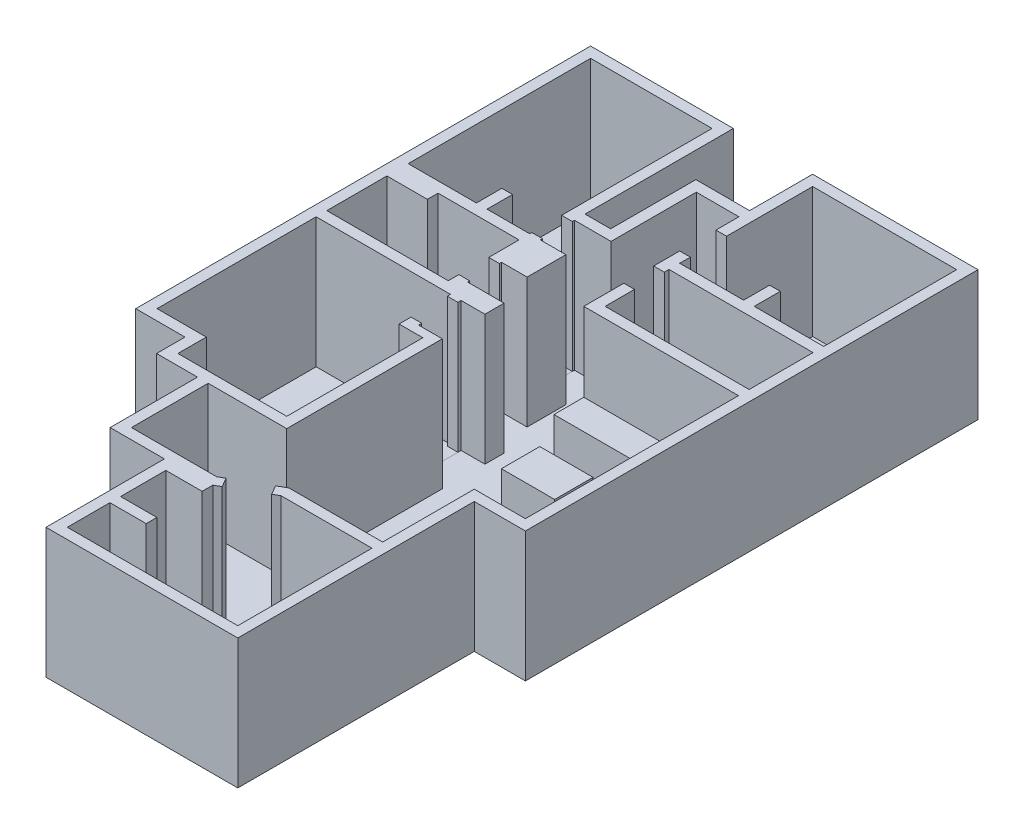
SolidWorks part; units mm, degrees
other "Long Room"
other "Corner Room"
other "Bathroom 1"
other "Big Room"
other "Window Room"
other "Walls"
other "Window Room Closet"
other "Long Room Closet"
other "Corner Room Closet"
other "Big Room Closet"
other "Bathroom 2"
ref_plane "Front Plane" through (0, 0, 0) normal (0, 0, 1) x (1, 0, 0)
ref_plane "Top Plane" through (0, 0, 0) normal (0, 1, 0) x (1, 0, 0)
ref_plane "Right Plane" through (0, 0, 0) normal (1, 0, 0) x (0, 0, -1)
sketch "Sketch1" plane through (0, 0, 0) normal (0, 1, 0) x (1, 0, 0)
  line L0 (0, 0) -> (0, -4280)
  line L1 (0, 0) -> (8590, 0) construction
  line L2 (0, 0) -> (0, -15669) construction
  line L3 (0, -15669) -> (8590, -15669) construction
  line L4 (8590, 0) -> (8590, -15669) construction
  line L5 (0, -4280) -> (1600, -4280)
  line L6 (1600, -4280) -> (1600, -3683)
  line L7 (1600, -3683) -> (1850, -3683)
  line L8 (2850, 0) -> (2850, -3530)
  line L9 (2850, -3530) -> (3100, -3530)
  line L11 (6710, -2510) -> (6710, -3120)
  line L12 (6710, -3120) -> (5210, -3120)
  line L13 (5210, -3480) -> (5210, -3370)
  line L14 (2850, 0) -> (0, 0)
  line L15 (5210, 0) -> (8590, 0)
  line L16 (8590, 0) -> (8590, -3120)
  line L17 (4241, -13106.5805) -> (4241, -13356.5805)
  line L18 (4116, -12890.0742) -> (4255.9329, -12809.2839)
  line L22 (8590, -3370) -> (8590, -4870)
  line L23 (5210, -4870) -> (8590, -4870)
  line L25 (0, -6190) -> (2850, -6190)
  line L26 (2850, -6190) -> (2850, -5940)
  line L27 (2850, -4530) -> (950, -4530)
  line L28 (0, -4780) -> (0, -6190)
  line L29 (950, -4530) -> (950, -4780)
  line L30 (1600, -3683) -> (0, -3683)
  line L31 (4255.9329, -12809.2839) -> (4380.9329, -13025.7903)
  line L32 (4241, -14419) -> (3390, -14419)
  line L33 (1850, -3683) -> (1850, -4280)
  line L34 (1850, -4280) -> (2850, -4280)
  line L35 (2850, -4280) -> (2850, -4230)
  line L36 (2850, -4230) -> (3100, -4230)
  line L37 (3100, -4230) -> (3100, -4280)
  line L38 (3100, -4280) -> (3700, -4280)
  line L39 (3100, -3530) -> (3100, -3480)
  line L40 (3100, -3480) -> (3960, -3480)
  line L41 (3960, -3480) -> (3960, -1480)
  line L42 (3960, -1480) -> (4960, -1480)
  line L43 (4960, -1480) -> (4960, -2020)
  line L45 (5210, -3120) -> (5210, -2870)
  line L46 (5210, -2870) -> (4960, -2870)
  line L47 (4960, -2870) -> (4960, -3480)
  line L48 (4960, -3480) -> (5210, -3480)
  line L49 (5210, -3480) -> (5210, -3370)
  line L50 (5210, -3370) -> (8590, -3370)
  line L51 (3700, -4280) -> (3700, -5190)
  line L52 (4960, -4180) -> (5210, -4180)
  line L53 (5210, -4180) -> (5210, -4870)
  line L54 (4960, -4180) -> (4960, -5120)
  line L55 (4960, -5120) -> (8590, -5120)
  line L56 (3700, -5190) -> (3100, -5190)
  line L57 (3100, -5190) -> (3100, -5240)
  line L58 (3100, -5240) -> (2850, -5240)
  line L59 (2850, -5240) -> (2850, -4530)
  line L60 (2850, -5940) -> (3100, -5940)
  line L61 (950, -4780) -> (0, -4780)
  line L62 (3100, -5940) -> (3100, -5990)
  line L63 (3100, -5990) -> (3960, -5990)
  line L64 (3960, -5990) -> (3960, -6440)
  line L65 (3960, -6440) -> (3401.2, -6440)
  line L66 (3401.2, -6440) -> (3401.2, -6515)
  line L67 (3401.2, -6515) -> (3151.2, -6515)
  line L68 (3151.2, -6515) -> (3151.2, -6440)
  line L69 (3151.2, -6440) -> (0, -6440)
  line L70 (1155.7, -10840.0742) -> (3710, -10840.0742)
  line L71 (3401.2, -7440) -> (3401.2, -7365)
  line L72 (3401.2, -7440) -> (3960, -7440)
  line L73 (3960, -7440) -> (3960, -11090.0742)
  line L74 (4380.9329, -13025.7903) -> (4241, -13106.5805)
  line L75 (3390, -14669) -> (4241, -14669)
  line L77 (4241, -14419) -> (4241, -14669)
  line L78 (3390, -14669) -> (3390, -15669)
  line L79 (3401.2, -7365) -> (3151.2, -7365)
  line L80 (3151.2, -7365) -> (3151.2, -7646.5)
  line L81 (3151.2, -7646.5) -> (3710, -7646.5)
  line L82 (3710, -7646.5) -> (3710, -10840.0742)
  line L83 (4116, -12890.0742) -> (2116, -12890.0742)
  line L84 (3960, -11090.0742) -> (2116, -11090.0742)
  line L86 (5117.0544, -12600.7903) -> (4992.0544, -12384.2839)
  line L89 (4992.0544, -12384.2839) -> (5190, -12270)
  line L90 (5190, -12270) -> (7390, -12270)
  line L91 (4255.9329, -12809.2839) -> (4992.0544, -12384.2839)
  line L92 (5117.0544, -12600.7903) -> (5256.9873, -12520)
  line L93 (5256.9873, -12520) -> (7390, -12520)
  line L94 (4241, -13356.5805) -> (3390, -13356.5805)
  line L95 (3390, -13356.5805) -> (3390, -14419)
  line L96 (4241, -13356.5805) -> (4241, -14419)
  line L97 (2116, -12890.0742) -> (2116, -11090.0742)
  line L98 (6710, -2510) -> (6960, -2510)
  line L99 (6960, -2510) -> (6960, -3120)
  line L100 (6960, -3120) -> (8590, -3120)
  line L101 (6960, -2510) -> (8590, -2510)
  line L102 (5210, -2020) -> (4960, -2020)
  line L103 (5210, -2020) -> (5210, 0)
  line L104 (4960, -2870) -> (4960, -3480)
  line L105 (5210, -3120) -> (5210, -2870)
  line L106 (8590, -5120) -> (8590, -10120)
  line L107 (8590, -10120) -> (7390, -10120)
  line L108 (7390, -10120) -> (7390, -12270)
  line L109 (7390, -12520) -> (7390, -15669)
  line L110 (7390, -15669) -> (3390, -15669)
  line L111 (4241, -13106.5805) -> (4116, -12890.0742) construction
  line L112 (3710, -10173.8) -> (0, -10173.8)
  line L113 (1155.7, -10840.0742) -> (1155.7, -10173.8)
  line L114 (0, -6440) -> (0, -10173.8)
  line L115 (1155.7, -10173.8) -> (0, -10173.8)
  line L116 (3401.2, -7365) -> (3401.2, -6515)
  line L117 (3100, -5940) -> (3100, -5240)
  line L118 (3100, -4230) -> (3100, -3530)
  line L119 (4960, -2870) -> (4960, -2020)
  line L120 (4960, -4180) -> (4960, -3480)
  dimension "D1" = 2850
  dimension "D2" = 150
  dimension "D3" = 4280
  dimension "D4" = 800
  dimension "D5" = 1000
  dimension "D6" = 600
  dimension "D7" = 860
  dimension "D8" = 1000
  dimension "D9" = 2000
  dimension "D10" = 250
  dimension "D11" = 250
  dimension "D12" = 250
  dimension "D13" = 558.8
  dimension "D14" = 250
  dimension "D15" = 250
  dimension "D16" = 3120
  dimension "D17" = 250
  dimension "D18" = 700
  dimension "D19" = 850
  dimension "D20" = 700
  dimension "D21" = 1500
  dimension "D22" = 3380
  dimension "D23" = 250
  dimension "D24" = 1500
  dimension "D25" = 1660
  dimension "D26" = 250
  dimension "D27" = 1206.5
  dimension "D28" = 5000
  dimension "D29" = 1000
  dimension "D30" = 250
  dimension "D31" = 3683
  dimension "D32" = 2510
  dimension "D33" = 450
  dimension "D34" = 250
  dimension "D35" = 4000
  dimension "D36" = 250
  dimension "D37" = 250
  dimension "D38" = 1200
  dimension "D39" = 2150
  dimension "D40" = 3149
  dimension "D41" = 3149
  dimension "D42" = 850
  dimension "D43" = 1000
  dimension "D44" = 250
  dimension "D45" = 2200
  dimension "D46" = 2000
  dimension "D47" = 1800
  dimension "D48" = 250
  dimension "D49" = 250
  dimension "D50" = 1900
  dimension "D51" = 700
  dimension "D52" = 250
  dimension "D53" = 850
  dimension "D54" = 2527.3
  dimension "D55" = 1155.7
extrude "Boss-Extrude1" add sketch "Sketch1" along normal blind 100 contours L36 L118 L9 L8 L14 L0 L5 L6 L7 L33 L34 L35 | L119 L46 L45 L12 L11 L98 L99 L100 L16 L15 L103 L102 | L60 L117 L58 L59 L27 L29 L61 L28 L25 L26 | L79 L116 L67 L68 L69 L114 L115 L113 L70 L82 L81 L80 | L110 L109 L93 L92 L86 L91 L31 L74 L17 L94 L95 L32 L77 L75 L78 | L120 L52 L53 L23 L22 L50 L13 L48 region at (1498.0773, 0, 1986.5335) region at (6770.383, 0, 1429.8229) region at (1531.4314, 0, 5404.487) region at (6839.4423, 0, 4110.3241) region at (1798.2254, 0, 8348.8303) region at (5668.1773, 0, 14190.9305)
extrude "Boss-Extrude2" add sketch "Sketch1<4>" along normal blind 100 separate body contours L54 L120 L47 L119 L43 L42 L41 L40 L39 L118 L37 L38 L51 L56 L57 L117 L62 L63 L64 L65 L66 L116 L71 L72 L73 L84 L97 L83 L18 L91 L89 L90 L108 L107 L106 L55 region at (5566.5772, 0, 8174.0459)
sketch "Sketch1<4>" plane through (0, 0, 0) normal (0, 1, 0) x (1, 0, 0) same geometry as "Sketch1"
extrude "Boss-Extrude4" add sketch "Sketch1<5>" along normal blind 100 separate body contours L6 L30 L0 L5 | L101 L99 L100 L16 | L113 L70 L82 L112 | L96 L94 L95 L32 region at (800, 0, 3981.5) region at (7775, 0, 2815) region at (2432.85, 0, 10506.9371) region at (3815.5, 0, 13887.7903)
sketch "Sketch1<5>" plane through (0, 0, 0) normal (0, 1, 0) x (1, 0, 0) same geometry as "Sketch1"
sketch "Sketch2" plane through (0, 100, 0) normal (0, 1, 0) x (1, 0, 0)
  line L0 (5210, -2020) -> (4960, -2020) construction
  line L1 (5210, -2020) -> (5210, 0) construction
  line L2 (5210, 0) -> (8590, 0) construction
  line L3 (8590, 0) -> (8590, -3120) construction
  line L4 (6960, -3120) -> (8590, -3120) construction
  line L5 (6960, -2510) -> (6960, -3120) construction
  line L6 (6710, -2510) -> (6960, -2510) construction
  line L7 (6710, -2510) -> (6710, -3120) construction
  line L8 (6710, -3120) -> (5210, -3120) construction
  line L9 (5210, -3120) -> (5210, -2870) construction
  line L10 (5210, -3120) -> (5210, -2870) construction
  line L11 (2850, -3530) -> (3100, -3530) construction
  line L12 (2850, 0) -> (2850, -3530) construction
  line L13 (2850, 0) -> (0, 0) construction
  line L14 (0, 0) -> (0, -4280) construction
  line L15 (0, -4280) -> (1600, -4280) construction
  line L16 (1600, -4280) -> (1600, -3683) construction
  line L17 (1600, -3683) -> (1850, -3683) construction
  line L18 (1850, -3683) -> (1850, -4280) construction
  line L19 (1850, -4280) -> (2850, -4280) construction
  line L20 (2850, -4280) -> (2850, -4230) construction
  line L21 (2850, -4230) -> (3100, -4230) construction
  line L22 (3100, -3530) -> (3100, -3480) construction
  line L23 (3100, -3480) -> (3960, -3480) construction
  line L24 (3960, -3480) -> (3960, -1480) construction
  line L25 (3960, -1480) -> (4960, -1480) construction
  line L26 (4960, -1480) -> (4960, -2020) construction
  line L27 (3100, -4230) -> (3100, -3530) construction
  line L28 (4116, -12890.0742) -> (4255.9329, -12809.2839) construction
  line L29 (4116, -12890.0742) -> (2116, -12890.0742) construction
  line L30 (2116, -12890.0742) -> (2116, -11090.0742) construction
  line L31 (3960, -11090.0742) -> (2116, -11090.0742) construction
  line L32 (3960, -7440) -> (3960, -11090.0742) construction
  line L33 (3401.2, -7440) -> (3960, -7440) construction
  line L34 (3401.2, -7440) -> (3401.2, -7365) construction
  line L35 (4255.9329, -12809.2839) -> (4380.9329, -13025.7903) construction
  line L36 (4380.9329, -13025.7903) -> (4241, -13106.5805) construction
  line L37 (4241, -13106.5805) -> (4241, -13356.5805) construction
  line L38 (4241, -13356.5805) -> (3390, -13356.5805) construction
  line L39 (3390, -13356.5805) -> (3390, -14419) construction
  line L40 (4241, -14419) -> (3390, -14419) construction
  line L41 (4241, -14419) -> (4241, -14669) construction
  line L42 (3390, -14669) -> (4241, -14669) construction
  line L43 (3390, -14669) -> (3390, -15669) construction
  line L44 (7390, -15669) -> (3390, -15669) construction
  line L45 (7390, -12520) -> (7390, -15669) construction
  line L46 (5256.9873, -12520) -> (7390, -12520) construction
  line L47 (5117.0544, -12600.7903) -> (5256.9873, -12520) construction
  line L48 (5117.0544, -12600.7903) -> (4992.0544, -12384.2839) construction
  line L49 (4255.9329, -12809.2839) -> (4992.0544, -12384.2839) construction
  line L50 (4960, -2870) -> (4960, -3480) construction
  line L51 (4960, -3480) -> (5210, -3480) construction
  line L52 (4960, -2870) -> (4960, -3480) construction
  line L53 (4960, -4180) -> (4960, -3480) construction
  line L54 (5210, -2870) -> (4960, -2870) construction
  line L55 (4960, -2870) -> (4960, -2020) construction
  line L56 (3100, -4230) -> (3100, -4280) construction
  line L57 (3100, -4280) -> (3700, -4280) construction
  line L58 (3700, -4280) -> (3700, -5190) construction
  line L59 (3700, -5190) -> (3100, -5190) construction
  line L60 (3100, -5190) -> (3100, -5240) construction
  line L61 (5210, -3480) -> (5210, -3370) construction
  line L62 (5210, -3480) -> (5210, -3370) construction
  line L63 (4960, -4180) -> (5210, -4180) construction
  line L64 (5210, -4180) -> (5210, -4870) construction
  line L65 (5210, -4870) -> (8590, -4870) construction
  line L66 (8590, -3370) -> (8590, -4870) construction
  line L67 (5210, -3370) -> (8590, -3370) construction
  line L68 (2850, -5940) -> (3100, -5940) construction
  line L69 (2850, -6190) -> (2850, -5940) construction
  line L70 (0, -6190) -> (2850, -6190) construction
  line L71 (0, -4780) -> (0, -6190) construction
  line L72 (950, -4780) -> (0, -4780) construction
  line L73 (950, -4530) -> (950, -4780) construction
  line L74 (2850, -4530) -> (950, -4530) construction
  line L75 (2850, -5240) -> (2850, -4530) construction
  line L76 (3100, -5240) -> (2850, -5240) construction
  line L77 (3100, -5940) -> (3100, -5240) construction
  line L78 (4960, -4180) -> (4960, -5120) construction
  line L79 (4960, -5120) -> (8590, -5120) construction
  line L80 (8590, -5120) -> (8590, -10120) construction
  line L81 (8590, -10120) -> (7390, -10120) construction
  line L82 (7390, -10120) -> (7390, -12270) construction
  line L83 (5190, -12270) -> (7390, -12270) construction
  line L84 (4992.0544, -12384.2839) -> (5190, -12270) construction
  line L85 (3100, -5940) -> (3100, -5990) construction
  line L86 (3100, -5990) -> (3960, -5990) construction
  line L87 (3960, -5990) -> (3960, -6440) construction
  line L88 (3960, -6440) -> (3401.2, -6440) construction
  line L89 (3401.2, -6440) -> (3401.2, -6515) construction
  line L90 (3401.2, -7365) -> (3151.2, -7365) construction
  line L91 (3151.2, -7365) -> (3151.2, -7646.5) construction
  line L92 (3151.2, -7646.5) -> (3710, -7646.5) construction
  line L93 (3710, -7646.5) -> (3710, -10840.0742) construction
  line L94 (1155.7, -10840.0742) -> (3710, -10840.0742) construction
  line L95 (1155.7, -10840.0742) -> (1155.7, -10173.8) construction
  line L96 (1155.7, -10173.8) -> (0, -10173.8) construction
  line L97 (0, -6440) -> (0, -10173.8) construction
  line L98 (3151.2, -6440) -> (0, -6440) construction
  line L99 (3151.2, -6515) -> (3151.2, -6440) construction
  line L100 (3401.2, -6515) -> (3151.2, -6515) construction
  line L101 (3401.2, -7365) -> (3401.2, -6515) construction
  line L102 (5210, -2020) -> (4960, -2020)
  line L103 (5210, -2020) -> (5210, 0)
  line L104 (5210, 0) -> (8590, 0)
  line L105 (8590, 0) -> (8590, -3120)
  line L106 (6960, -3120) -> (8590, -3120)
  line L107 (6960, -2510) -> (6960, -3120)
  line L108 (6710, -2510) -> (6960, -2510)
  line L109 (6710, -2510) -> (6710, -3120)
  line L110 (6710, -3120) -> (5210, -3120)
  line L111 (5210, -3120) -> (5210, -2870)
  line L112 (5210, -3120) -> (5210, -2870)
  line L113 (2850, -3530) -> (3100, -3530)
  line L114 (2850, 0) -> (2850, -3530)
  line L115 (2850, 0) -> (0, 0)
  line L116 (0, 0) -> (0, -4280)
  line L117 (0, -4280) -> (1600, -4280)
  line L118 (1600, -4280) -> (1600, -3683)
  line L119 (1600, -3683) -> (1850, -3683)
  line L120 (1850, -3683) -> (1850, -4280)
  line L121 (1850, -4280) -> (2850, -4280)
  line L122 (2850, -4280) -> (2850, -4230)
  line L123 (2850, -4230) -> (3100, -4230)
  line L124 (3100, -3530) -> (3100, -3480)
  line L125 (3100, -3480) -> (3960, -3480)
  line L126 (3960, -3480) -> (3960, -1480)
  line L127 (3960, -1480) -> (4960, -1480)
  line L128 (4960, -1480) -> (4960, -2020)
  line L129 (3100, -4230) -> (3100, -3530)
  line L130 (4116, -12890.0742) -> (4255.9329, -12809.2839)
  line L131 (4116, -12890.0742) -> (2116, -12890.0742)
  line L132 (2116, -12890.0742) -> (2116, -11090.0742)
  line L133 (3960, -11090.0742) -> (2116, -11090.0742)
  line L134 (3960, -7440) -> (3960, -11090.0742)
  line L135 (3401.2, -7440) -> (3960, -7440)
  line L136 (3401.2, -7440) -> (3401.2, -7365)
  line L137 (4255.9329, -12809.2839) -> (4380.9329, -13025.7903)
  line L138 (4380.9329, -13025.7903) -> (4241, -13106.5805)
  line L139 (4241, -13106.5805) -> (4241, -13356.5805)
  line L140 (4241, -13356.5805) -> (3390, -13356.5805)
  line L141 (3390, -13356.5805) -> (3390, -14419)
  line L142 (4241, -14419) -> (3390, -14419)
  line L143 (4241, -14419) -> (4241, -14669)
  line L144 (3390, -14669) -> (4241, -14669)
  line L145 (3390, -14669) -> (3390, -15669)
  line L146 (7390, -15669) -> (3390, -15669)
  line L147 (7390, -12520) -> (7390, -15669)
  line L148 (5256.9873, -12520) -> (7390, -12520)
  line L149 (5117.0544, -12600.7903) -> (5256.9873, -12520)
  line L150 (5117.0544, -12600.7903) -> (4992.0544, -12384.2839)
  line L151 (4255.9329, -12809.2839) -> (4992.0544, -12384.2839)
  line L152 (4960, -2870) -> (4960, -3480)
  line L153 (4960, -3480) -> (5210, -3480)
  line L154 (4960, -2870) -> (4960, -3480)
  line L155 (4960, -4180) -> (4960, -3480)
  line L156 (5210, -2870) -> (4960, -2870)
  line L157 (4960, -2870) -> (4960, -2020)
  line L158 (3100, -4230) -> (3100, -4280)
  line L159 (3100, -4280) -> (3700, -4280)
  line L160 (3700, -4280) -> (3700, -5190)
  line L161 (3700, -5190) -> (3100, -5190)
  line L162 (3100, -5190) -> (3100, -5240)
  line L163 (5210, -3480) -> (5210, -3370)
  line L164 (5210, -3480) -> (5210, -3370)
  line L165 (4960, -4180) -> (5210, -4180)
  line L166 (5210, -4180) -> (5210, -4870)
  line L167 (5210, -4870) -> (8590, -4870)
  line L168 (8590, -3370) -> (8590, -4870)
  line L169 (5210, -3370) -> (8590, -3370)
  line L170 (2850, -5940) -> (3100, -5940)
  line L171 (2850, -6190) -> (2850, -5940)
  line L172 (0, -6190) -> (2850, -6190)
  line L173 (0, -4780) -> (0, -6190)
  line L174 (950, -4780) -> (0, -4780)
  line L175 (950, -4530) -> (950, -4780)
  line L176 (2850, -4530) -> (950, -4530)
  line L177 (2850, -5240) -> (2850, -4530)
  line L178 (3100, -5240) -> (2850, -5240)
  line L179 (3100, -5940) -> (3100, -5240)
  line L180 (4960, -4180) -> (4960, -5120)
  line L181 (4960, -5120) -> (8590, -5120)
  line L182 (8590, -5120) -> (8590, -10120)
  line L183 (8590, -10120) -> (7390, -10120)
  line L184 (7390, -10120) -> (7390, -12270)
  line L185 (5190, -12270) -> (7390, -12270)
  line L186 (4992.0544, -12384.2839) -> (5190, -12270)
  line L187 (3100, -5940) -> (3100, -5990)
  line L188 (3100, -5990) -> (3960, -5990)
  line L189 (3960, -5990) -> (3960, -6440)
  line L190 (3960, -6440) -> (3401.2, -6440)
  line L191 (3401.2, -6440) -> (3401.2, -6515)
  line L192 (3401.2, -7365) -> (3151.2, -7365)
  line L193 (3151.2, -7365) -> (3151.2, -7646.5)
  line L194 (3151.2, -7646.5) -> (3710, -7646.5)
  line L195 (3710, -7646.5) -> (3710, -10840.0742)
  line L196 (1155.7, -10840.0742) -> (3710, -10840.0742)
  line L197 (1155.7, -10840.0742) -> (1155.7, -10173.8)
  line L198 (1155.7, -10173.8) -> (0, -10173.8)
  line L199 (0, -6440) -> (0, -10173.8)
  line L200 (3151.2, -6440) -> (0, -6440)
  line L201 (3151.2, -6515) -> (3151.2, -6440)
  line L202 (3401.2, -6515) -> (3151.2, -6515)
  line L203 (3401.2, -7365) -> (3401.2, -6515)
  line L204 (-250, -10423.8) -> (905.7, -10423.8)
  line L205 (905.7, -10423.8) -> (905.7, -11090.0742)
  line L206 (905.7, -11090.0742) -> (1866, -11090.0742)
  line L207 (1866, -11090.0742) -> (1866, -13140.0742)
  line L208 (1866, -13140.0742) -> (3140, -13140.0742)
  line L209 (3140, -13140.0742) -> (3140, -15919)
  line L210 (8840, -10370) -> (7640, -10370)
  line L211 (7640, -10370) -> (7640, -15919)
  line L212 (4960, 250) -> (4960, -1230)
  line L213 (4960, -1230) -> (3700, -1230)
  line L214 (-250, 250) -> (3100, 250)
  line L215 (-250, 250) -> (-250, -10423.8)
  line L216 (3140, -15919) -> (7640, -15919)
  line L217 (8840, 250) -> (8840, -10370)
  line L218 (3700, -1230) -> (3700, -3230)
  line L219 (3700, -3230) -> (3100, -3230)
  line L220 (3100, -3230) -> (3100, 250)
  line L221 (4960, 250) -> (8840, 250)
  line M1 (4960, -5120) -> (4960, -1480)
  line M2 (4960, -1480) -> (3960, -1480)
  line M3 (3960, -1480) -> (3960, -3480)
  line M4 (3960, -3480) -> (3100, -3480)
  line M5 (3100, -3480) -> (3100, -4280)
  line M6 (3100, -4280) -> (3700, -4280)
  line M7 (3700, -4280) -> (3700, -5190)
  line M8 (3700, -5190) -> (3100, -5190)
  line M9 (3100, -5190) -> (3100, -5990)
  line M10 (3100, -5990) -> (3960, -5990)
  line M11 (3960, -5990) -> (3960, -6440)
  line M12 (3960, -6440) -> (3401.2, -6440)
  line M13 (3401.2, -6440) -> (3401.2, -7440)
  dimension "D1" = 250
  dimension "D2" = 250
  dimension "D3" = 250
  dimension "D4" = 250
  dimension "D5" = 250
  dimension "D6" = 250
  dimension "D7" = 250
  dimension "D8" = 250
  dimension "D9" = 250
  dimension "D10" = 250
  dimension "D11" = 250
  dimension "D12" = 250
  dimension "D13" = 250
  dimension "D14" = 250
  dimension "D15" = 250
  dimension "D16" = 250
extrude "Boss-Extrude3" add sketch "Sketch2" along normal blind 3048 separate body contours L217 L214 L215 L216 L202 L170 L171 L172 L173 L174 L175 L176 L177 L178 L123 L122 L121 L120 L119 L118 L117 L116 L115 L114 L113 L102 L103 L104 L105 L106 L107 L108 L109 L110 L111 M13 M12 M11 M10 M9 M8 M7 M6 M5 M4 M3 M2 M1 region at (-64.5102, 100, 5086.9)
sketch "Sketch5" plane through (0, 100, 0) normal (0, 1, 0) x (1, 0, 0)
  line L0 (8590, -7120) -> (7890, -7120)
  line L1 (5444.7619, -6637.9805) -> (6694.7619, -6637.9805)
  line L2 (5444.7619, -6637.9805) -> (5444.7619, -7537.9805)
  line L3 (5444.7619, -7537.9805) -> (6694.7619, -7537.9805)
  line L4 (6694.7619, -6637.9805) -> (6694.7619, -7537.9805)
  line L5 (8590, -10120) -> (8590, -5120) construction
  line L6 (7890, -7120) -> (7890, -5820)
  line L7 (7890, -5820) -> (4960, -5820)
  line L8 (4960, -5820) -> (4960, -5120)
  line L9 (4960, -5120) -> (8590, -5120)
  line L10 (8590, -5120) -> (8590, -7120)
  line L11 (0, -6190) -> (2850, -6190) construction
  line L12 (0, -4780) -> (950, -4780)
  line L13 (0, -4780) -> (0, -6190)
  line L14 (0, -6190) -> (950, -6190)
  line L15 (950, -4780) -> (950, -6190)
  line L16 (5210, -3370) -> (8590, -3370) construction
  line L17 (8590, -4870) -> (7640, -4870)
  line L18 (8590, -4870) -> (8590, -3370)
  line L19 (8590, -3370) -> (7640, -3370)
  line L20 (7640, -4870) -> (7640, -3370)
  line L21 (8490, -4770) -> (8490, -3470)
  line L22 (8490, -3470) -> (7740, -3470)
  line L23 (7740, -4770) -> (7740, -3470)
  line L24 (8490, -4770) -> (7740, -4770)
  line L25 (100, -4880) -> (100, -6090)
  line L26 (100, -6090) -> (850, -6090)
  line L27 (850, -4880) -> (850, -6090)
  line L28 (100, -4880) -> (850, -4880)
  line M41 (8590, -10120) -> (8590, -5120)
  line M42 (8590, -5120) -> (4960, -5120)
  dimension "D1" = 900
  dimension "D2" = 1250
  dimension "D3" = 2000
  dimension "D4" = 700
  dimension "D5" = 700
  dimension "D6" = 100
extrude "Boss-Extrude7" add sketch "Sketch5" along normal blind 1200 contours L4 L1 L2 L3 | L8 L7 L6 L0 M41 M42 region at (7161.3083, 100, 5733.6917) region at (6069.7619, 100, 7087.9805)
extrude "Boss-Extrude9" add sketch "Sketch5<3>" along normal blind 800 contours L15 L12 L13 L14 L25 L28 L27 L26 region at (475, 100, 4797.0018)
sketch "Sketch5<3>" plane through (0, 100, 0) normal (0, 1, 0) x (1, 0, 0) same geometry as "Sketch5"
extrude "Boss-Extrude10" add sketch "Sketch5<4>" along normal blind 800 contours L20 L17 L18 L19 L21 L24 L23 L22 region at (8115, 100, 4852.2447)
sketch "Sketch5<4>" plane through (0, 100, 0) normal (0, 1, 0) x (1, 0, 0) same geometry as "Sketch5"
